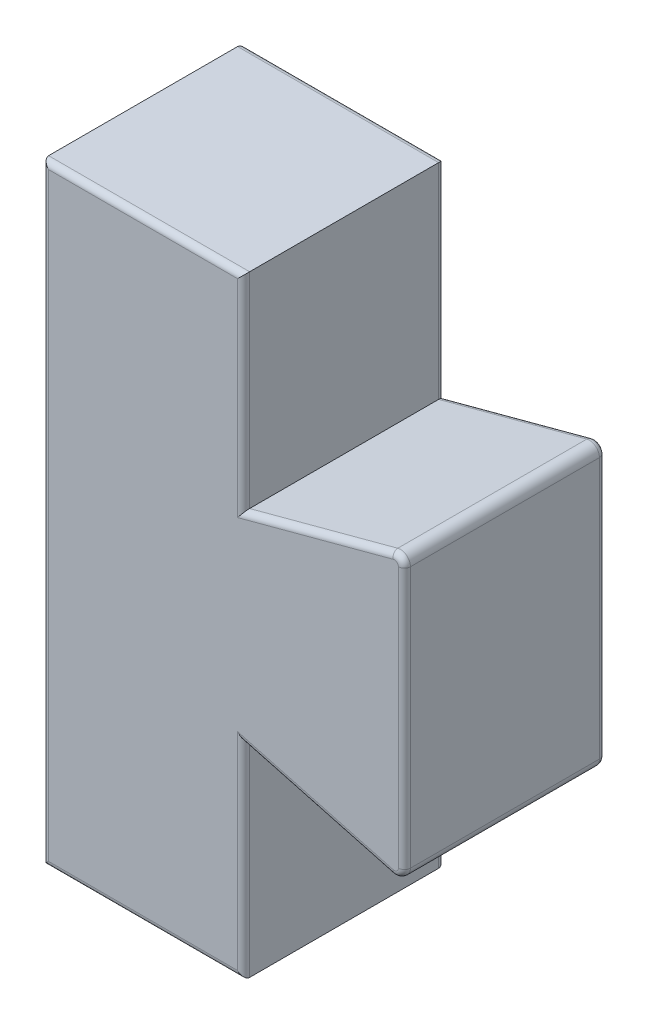
SolidWorks part; units mm, degrees
ref_plane "Plan de face" through (0, 0, 0) normal (0, 0, 1) x (1, 0, 0)
ref_plane "Plan de dessus" through (0, 0, 0) normal (0, 1, 0) x (1, 0, 0)
ref_plane "Plan de droite" through (0, 0, 0) normal (1, 0, 0) x (0, 0, -1)
sketch "Esquisse1" plane through (0, 0, 0) normal (0, 0, 1) x (1, 0, 0)
  line L0 (10, 20.2) -> (18, 22.3436)
  line L1 (0, 0) -> (10, 0)
  line L2 (0, 0) -> (0, 30.4)
  line L3 (0, 30.4) -> (10, 30.4)
  line L4 (10, 0) -> (10, 10.2)
  line L5 (18, 22.3436) -> (18, 8.0564)
  line L6 (18, 8.0564) -> (10, 10.2)
  line L7 (10, 20.2) -> (10, 30.4)
  point P7 (0, 0)
  point P10 (0, 0)
  point P11 (10, 20.4832)
  point P12 (10, 9.7977)
  dimension "D1" = 75
  dimension "D2" = 75
  dimension "D3" = 8
  dimension "D4" = 10
  dimension "D5" = 10
  dimension "D6" = 30.4
  dimension "D7" = 10.2
extrude "Boss.-Extru.1" add sketch "Esquisse1" along normal blind 10
fillet "Congé1" radius 0.3 16 edges at (5, 0, 0) (10, 5.1, 0) (14, 9.1282, 0) (18, 15.2, 0) (14, 21.2718, 0) (10, 25.3, 0) (5, 30.4, 0) (0, 15.2, 0) (5, 30.4, 10) (10, 25.3, 10) (14, 21.2718, 10) (18, 15.2, 10) (14, 9.1282, 10) (10, 5.1, 10) (5, 0, 10) (0, 15.2, 10)
fillet "Congé2" radius 0.5 6 edges at (17.9121, 22.2291, 0.0879) (17.9121, 22.2291, 9.9121) (17.9121, 8.1709, 0.0879) (17.9121, 8.1709, 9.9121) (18, 8.0564, 5) (18, 22.3436, 5)
